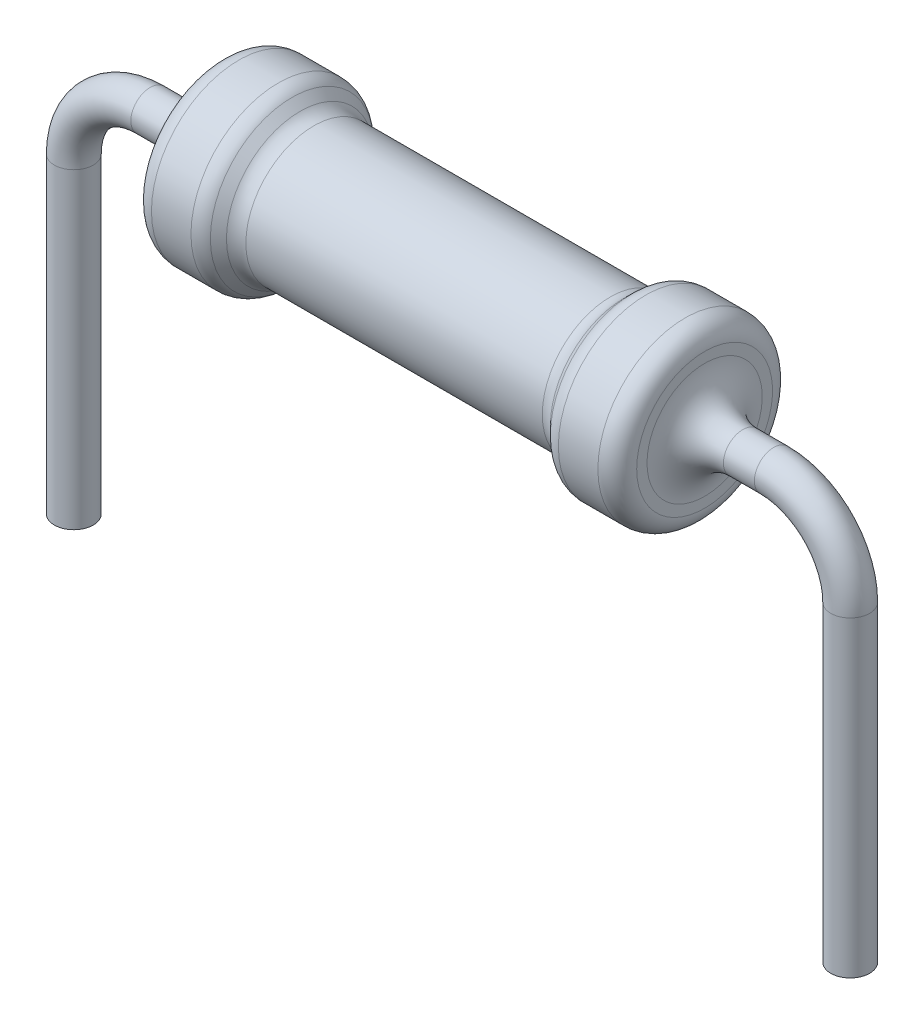
SolidWorks part; units mm, degrees
ref_plane "Front Plane" through (0, 0, 0) normal (0, 0, 1) x (1, 0, 0)
ref_plane "Top Plane" through (0, 0, 0) normal (0, 1, 0) x (1, 0, 0)
ref_plane "Right Plane" through (0, 0, 0) normal (1, 0, 0) x (0, 0, -1)
sketch "Sketch1" plane through (0, 0, 0) normal (0, 0, 1) x (1, 0, 0)
  line L0 (-13.0515, 0) -> (13.0515, 0) construction
  line L1 (0, 5.0096) -> (0, -5.0096) construction
  line L2 (1.9396, 0.889) -> (-1.9396, 0.889)
  line L3 (3.175, 0.889) -> (3.175, 0)
  line L4 (2.2244, 1.0686) -> (2.1192, 0.9634)
  line L5 (-1.9396, 0.889) -> (-3.175, 0.889) construction
  line L6 (1.9396, 0.889) -> (3.175, 0.889) construction
  line L7 (2.404, 1.143) -> (2.921, 1.143)
  line L8 (3.175, 0) -> (-3.175, 0)
  line L9 (-2.404, 1.143) -> (-2.921, 1.143)
  line L10 (-2.2244, 1.0686) -> (-2.1192, 0.9634)
  line L11 (-3.175, 0.889) -> (-3.175, 0)
  arc A0 (2.921, 1.143) -> (3.175, 0.889) centre (2.921, 0.889) cw
  arc A1 (2.2244, 1.0686) -> (2.404, 1.143) centre (2.404, 0.889) cw
  arc A2 (-1.9396, 0.889) -> (-2.1192, 0.9634) centre (-1.9396, 1.143) cw
  arc A3 (-2.2244, 1.0686) -> (-2.404, 1.143) centre (-2.404, 0.889) ccw
  arc A4 (1.9396, 0.889) -> (2.1192, 0.9634) centre (1.9396, 1.143) ccw
  arc A5 (-2.921, 1.143) -> (-3.175, 0.889) centre (-2.921, 0.889) ccw
  point P12 (0, 0)
  point P13 (-2.0448, 0.889)
  point P19 (0, 0.889)
  point P24 (2.0448, 0.889)
  point P29 (0, 0.889)
  dimension "D1" = 0.889
  dimension "D2" = 0.254
  dimension "D3" = 0.254
  dimension "D4" = 3.175
  dimension "D5" = 0.1488
  dimension "D6" = 45
revolve "Revolve1" add sketch "Sketch1" angle 360 about L0
sketch "Sketch2" plane through (0, 0, 0) normal (0, 0, 1) x (1, 0, 0)
  line L0 (4.08, 0) -> (0, 0)
  line L2 (0, -1000) -> (0, 49000) construction
  line L3 (5.08, -1) -> (5.08, -5.08)
  arc A1 (4.08, 0) -> (5.08, -1) centre (4.08, -1) cw
  point P7 (-5.08, 0)
  point P14 (0, 0)
  dimension "D1" = 5.08
sketch "Sketch3" plane through (0, 0, 0) normal (1, 0, 0) x (0, 0, -1)
  circle A0 centre (0, 0) radius 0.254
  dimension "D1" = 0.508
sweep "Sweep1" add profiles "Sketch3" path "Sketch2"
mirror "Mirror1" about plane through (0, 0, 0) normal (1, 0, 0) of "Sweep1"
fillet "Fillet1" radius 0.5 2 edges at (3.175, 0, 0.254) (-3.175, 0, -0.254)
ref_axis "Center Line" through (1.9396, 0, 0) along (-1, 0, 0)
